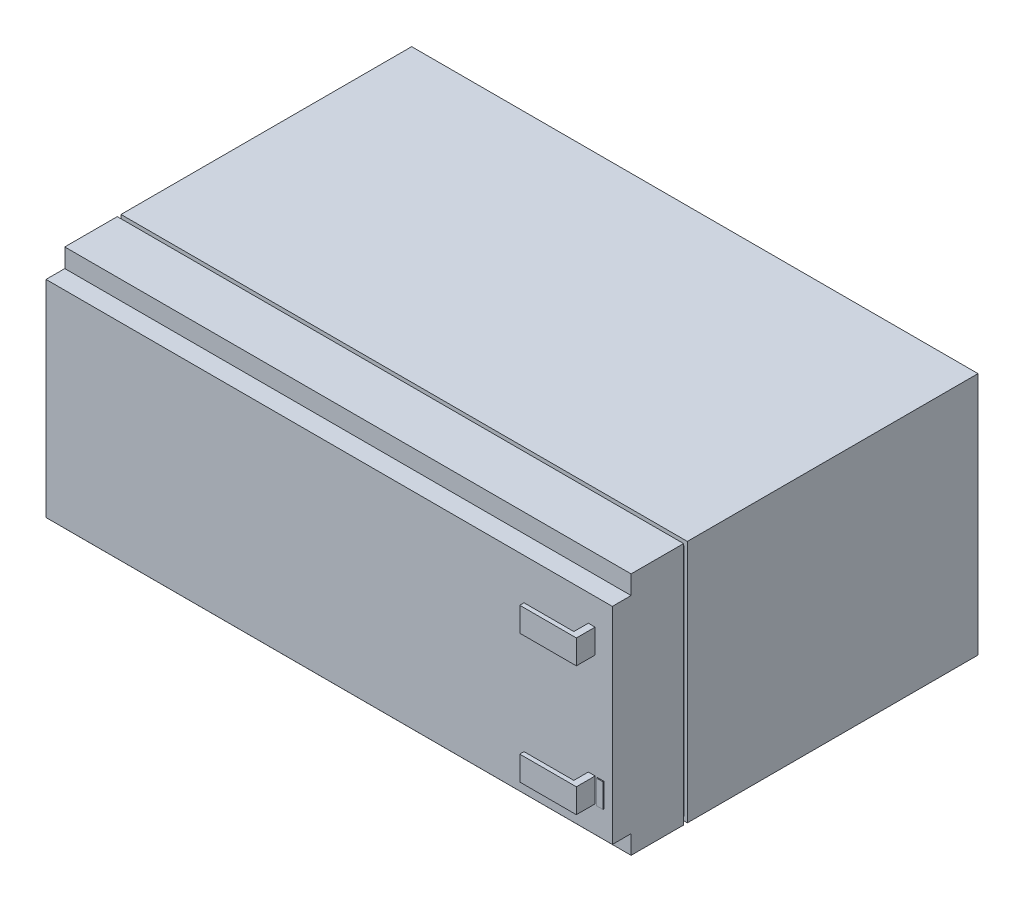
SolidWorks part; units mm, degrees
ref_plane "Plan de face" through (0, 0, 0) normal (0, 0, 1) x (1, 0, 0)
ref_plane "Plan de dessus" through (0, 0, 0) normal (0, 1, 0) x (1, 0, 0)
ref_plane "Plan de droite" through (0, 0, 0) normal (1, 0, 0) x (0, 0, -1)
sketch "Esquisse1" plane through (0, 0, 0) normal (0, 0, 1) x (1, 0, 0)
  line L1 (0, 0) -> (151, 0)
  line L2 (0, 0) -> (0, 65)
  line L3 (0, 65) -> (151, 65)
  line L4 (151, 0) -> (151, 65)
  dimension "D1" = 151
  dimension "D2" = 65
extrude "Boss.-Extru.1" add sketch "Esquisse1" along normal blind 77.5
sketch "Esquisse3" plane through (0, 0, 77.5) normal (0, 0, 1) x (1, 0, 0)
  line L1 (150.0492, 1.027) -> (1.5943, 1.027)
  line L2 (150.0492, 1.027) -> (150.0492, 63.6077)
  line L3 (150.0492, 63.6077) -> (1.5943, 63.6077)
  line L4 (1.5943, 1.027) -> (1.5943, 63.6077)
extrude "Boss.-Extru.4" add sketch "Esquisse3" along normal blind 1
sketch "Esquisse4" plane through (0, 0, 78.5) normal (0, 0, 1) x (1, 0, 0)
  line L1 (151, 0) -> (0, 0)
  line L2 (151, 0) -> (151, 65)
  line L3 (151, 65) -> (0, 65)
  line L4 (0, 0) -> (0, 65)
extrude "Boss.-Extru.5" add sketch "Esquisse4" along normal blind 19
sketch "Esquisse5" plane through (151, 0, 0) normal (1, 0, 0) x (0, 0, -1)
  line L0 (-97.5, 0) -> (-92.4951, 0) construction
  line L1 (-97.5, 0) -> (-78.5, 0) construction
  line L2 (-92.4951, 0) -> (-92.4951, 65) construction
  line L3 (-97.5, 65) -> (-78.5, 65) construction
  line L4 (-92.4951, 65) -> (-97.5, 65) construction
  line L5 (-97.5, 65) -> (-97.5, 59.9995) construction
  line L6 (-97.5, 0) -> (-97.5, 65) construction
  line L7 (-97.5, 59.9995) -> (-92.4951, 59.9995) construction
  line L8 (-97.5, 0) -> (-97.5, 5.0139) construction
  line L9 (-97.5, 5.0139) -> (-92.4951, 5.0139) construction
  line L11 (-97.5, 0) -> (-92.4951, 0)
  line L12 (-97.5, 0) -> (-97.5, 5.0139)
  line L13 (-97.5, 5.0139) -> (-92.4951, 5.0139)
  line L14 (-92.4951, 0) -> (-92.4951, 5.0139)
  line L15 (-97.5, 65) -> (-92.4951, 65)
  line L16 (-97.5, 65) -> (-97.5, 59.9995)
  line L17 (-97.5, 59.9995) -> (-92.4951, 59.9995)
  line L18 (-92.4951, 65) -> (-92.4951, 59.9995)
extrude "Enlèv. mat.-Extru.1" cut sketch "Esquisse5" against normal blind 159
sketch "Esquisse6" plane through (0, 0, 97.5) normal (0, 0, 1) x (1, 0, 0)
  line L0 (151, 32.5067) -> (0, 32.5067) construction
  line L1 (151, 5.0139) -> (151, 59.9995) construction
  line L2 (0, 59.9995) -> (0, 5.0139) construction
  line L3 (146.409, 46.4677) -> (131.3171, 46.4677)
  line L4 (146.409, 12.0994) -> (131.3171, 12.0994)
  line L5 (146.409, 12.0994) -> (146.409, 18.5457)
  line L6 (146.409, 18.5457) -> (131.3171, 18.5457)
  line L7 (131.3171, 12.0994) -> (131.3171, 18.5457)
  line L8 (131.3171, 52.914) -> (131.3171, 46.4677)
  line L9 (146.409, 52.914) -> (131.3171, 52.914)
  line L10 (146.409, 52.914) -> (146.409, 46.4677)
extrude "Boss.-Extru.6" add sketch "Esquisse6" along normal blind 5
sketch "Esquisse7" plane through (0, 52.914, 0) normal (0, 1, 0) x (1, 0, 0)
  line L0 (131.3171, -102.5) -> (131.3171, -97.5) construction
  line L1 (131.3171, -101.3609) -> (144.5982, -101.3609)
  line L2 (131.3171, -101.3609) -> (131.3171, -97.5)
  line L3 (131.3171, -97.5) -> (144.5982, -97.5)
  line L4 (144.5982, -101.3609) -> (144.5982, -97.5)
  line L5 (146.409, -97.5) -> (131.3171, -97.5) construction
extrude "Enlèv. mat.-Extru.2" cut sketch "Esquisse7" against normal blind 45
sketch "Esquisse8" plane through (0, 0, 97.5) normal (0, 0, 1) x (1, 0, 0)
  line L1 (146.9983, 12.0994) -> (148.7747, 12.0994)
  line L2 (146.9983, 12.0994) -> (146.9983, 18.4992)
  line L3 (146.9983, 18.4992) -> (148.7747, 18.4992)
  line L4 (148.7747, 12.0994) -> (148.7747, 18.4992)
extrude "Boss.-Extru.7" add sketch "Esquisse8" along normal blind 0.25
sketch "Esquisse9" plane through (0, 0, 97.5) normal (0, 0, 1) x (1, 0, 0)
  line L0 (0, 32.5067) -> (158.4851, 32.5067) construction
  line L1 (0, 59.9995) -> (0, 5.0139) construction
ref_axis "Axe1" through (0, 32.5067, 97.5) along (1, 0, 0)
